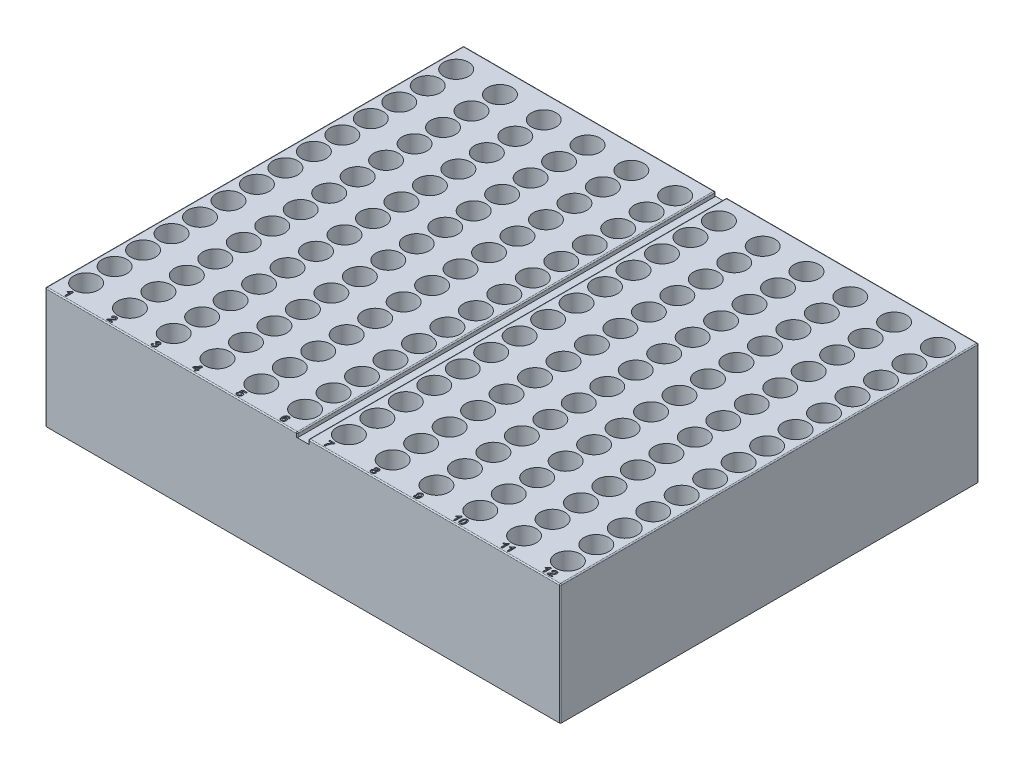
SolidWorks part; units mm, degrees
ref_plane "Front Plane" through (0, 0, 0) normal (0, 0, 1) x (1, 0, 0)
ref_plane "Top Plane" through (0, 0, 0) normal (0, 1, 0) x (1, 0, 0)
ref_plane "Right Plane" through (0, 0, 0) normal (1, 0, 0) x (0, 0, -1)
sketch "Sketch1" plane through (0, 0, 0) normal (0, 1, 0) x (1, 0, 0)
  line L0 (-50, 84.5) -> (-57.625, 84.5) construction
  line L1 (57.625, -95.5) -> (-57.625, -95.5)
  line L2 (57.625, -95.5) -> (57.625, 95.5)
  line L3 (57.625, 95.5) -> (-57.625, 95.5)
  line L4 (-57.625, -95.5) -> (-57.625, 95.5)
  line L5 (57.625, -95.5) -> (-57.625, 95.5) construction
  line L6 (57.625, 95.5) -> (-57.625, -95.5) construction
  line L7 (50, 84.5) -> (57.625, 84.5) construction
  line L8 (-50, 84.5) -> (-50, 95.5) construction
  line L9 (-30, 84.5) -> (-44.35, 84.5) construction
  line L10 (-50, -84.5) -> (-57.625, -84.5) construction
  line L11 (-50, -84.5) -> (-50, -95.5) construction
  circle A0 centre (-50, 84.5) radius 5.65
  circle A1 centre (-30, 84.5) radius 5.65
  circle A2 centre (-10, 84.5) radius 5.65
  circle A3 centre (10, 84.5) radius 5.65
  circle A4 centre (30, 84.5) radius 5.65
  circle A5 centre (50, 84.5) radius 5.65
  circle A6 centre (-50, 71.5) radius 5.65
  circle A7 centre (-30, 71.5) radius 5.65
  circle A8 centre (-10, 71.5) radius 5.65
  circle A9 centre (10, 71.5) radius 5.65
  circle A10 centre (30, 71.5) radius 5.65
  circle A11 centre (50, 71.5) radius 5.65
  circle A12 centre (-50, 58.5) radius 5.65
  circle A13 centre (-30, 58.5) radius 5.65
  circle A14 centre (-10, 58.5) radius 5.65
  circle A15 centre (10, 58.5) radius 5.65
  circle A16 centre (30, 58.5) radius 5.65
  circle A17 centre (50, 58.5) radius 5.65
  circle A18 centre (-50, 45.5) radius 5.65
  circle A19 centre (-30, 45.5) radius 5.65
  circle A20 centre (-10, 45.5) radius 5.65
  circle A21 centre (10, 45.5) radius 5.65
  circle A22 centre (30, 45.5) radius 5.65
  circle A23 centre (50, 45.5) radius 5.65
  circle A24 centre (-50, 32.5) radius 5.65
  circle A25 centre (-30, 32.5) radius 5.65
  circle A26 centre (-10, 32.5) radius 5.65
  circle A27 centre (10, 32.5) radius 5.65
  circle A28 centre (30, 32.5) radius 5.65
  circle A29 centre (50, 32.5) radius 5.65
  circle A30 centre (-50, 19.5) radius 5.65
  circle A31 centre (-30, 19.5) radius 5.65
  circle A32 centre (-10, 19.5) radius 5.65
  circle A33 centre (10, 19.5) radius 5.65
  circle A34 centre (30, 19.5) radius 5.65
  circle A35 centre (50, 19.5) radius 5.65
  circle A36 centre (-50, 6.5) radius 5.65
  circle A37 centre (-30, 6.5) radius 5.65
  circle A38 centre (-10, 6.5) radius 5.65
  circle A39 centre (10, 6.5) radius 5.65
  circle A40 centre (30, 6.5) radius 5.65
  circle A41 centre (50, 6.5) radius 5.65
  circle A42 centre (-50, -6.5) radius 5.65
  circle A43 centre (-30, -6.5) radius 5.65
  circle A44 centre (-10, -6.5) radius 5.65
  circle A45 centre (10, -6.5) radius 5.65
  circle A46 centre (30, -6.5) radius 5.65
  circle A47 centre (50, -6.5) radius 5.65
  circle A48 centre (-50, -19.5) radius 5.65
  circle A49 centre (-30, -19.5) radius 5.65
  circle A50 centre (-10, -19.5) radius 5.65
  circle A51 centre (10, -19.5) radius 5.65
  circle A52 centre (30, -19.5) radius 5.65
  circle A53 centre (50, -19.5) radius 5.65
  circle A54 centre (-50, -32.5) radius 5.65
  circle A55 centre (-30, -32.5) radius 5.65
  circle A56 centre (-10, -32.5) radius 5.65
  circle A57 centre (10, -32.5) radius 5.65
  circle A58 centre (30, -32.5) radius 5.65
  circle A59 centre (50, -32.5) radius 5.65
  circle A60 centre (-50, -45.5) radius 5.65
  circle A61 centre (-30, -45.5) radius 5.65
  circle A62 centre (-10, -45.5) radius 5.65
  circle A63 centre (10, -45.5) radius 5.65
  circle A64 centre (30, -45.5) radius 5.65
  circle A65 centre (50, -45.5) radius 5.65
  circle A66 centre (-50, -58.5) radius 5.65
  circle A67 centre (-30, -58.5) radius 5.65
  circle A68 centre (-10, -58.5) radius 5.65
  circle A69 centre (10, -58.5) radius 5.65
  circle A70 centre (30, -58.5) radius 5.65
  circle A71 centre (50, -58.5) radius 5.65
  circle A72 centre (-50, -71.5) radius 5.65
  circle A73 centre (-30, -71.5) radius 5.65
  circle A74 centre (-10, -71.5) radius 5.65
  circle A75 centre (10, -71.5) radius 5.65
  circle A76 centre (30, -71.5) radius 5.65
  circle A77 centre (50, -71.5) radius 5.65
  circle A78 centre (-50, -84.5) radius 5.65
  circle A79 centre (-30, -84.5) radius 5.65
  circle A80 centre (-10, -84.5) radius 5.65
  circle A81 centre (10, -84.5) radius 5.65
  circle A82 centre (30, -84.5) radius 5.65
  circle A83 centre (50, -84.5) radius 5.65
  point P0 (0, 0)
  dimension "D1" = 11.3
  dimension "D3" = 20
  dimension "D7" = 191
  dimension "D8" = 13
  dimension "D9" = 115.25
  dimension "D2" = 6
  dimension "D6" = 14
extrude "Boss-Extrude1" add sketch "Sketch1" along normal blind 10
sketch "Sketch2" plane through (0, 0, 0) normal (0, -1, 0) x (1, 0, 0)
  line L1 (57.625, -95.5) -> (-57.625, -95.5)
  line L2 (57.625, -95.5) -> (57.625, 95.5)
  line L3 (57.625, 95.5) -> (-57.625, 95.5)
  line L4 (-57.625, -95.5) -> (-57.625, 95.5)
  line L5 (57.625, -95.5) -> (-57.625, 95.5) construction
  line L6 (57.625, 95.5) -> (-57.625, -95.5) construction
  point P0 (0, 0)
extrude "Boss-Extrude2" add sketch "Sketch2" along normal blind 45
sketch "Sketch6" plane through (0, 0, 0) normal (0, 1, 0) x (1, 0, 0)
  circle A1 centre (-50, 84.5) radius 4.225
  circle A2 centre (-30, 84.5) radius 4.225
  circle A3 centre (-10, 84.5) radius 4.225
  circle A4 centre (10, 84.5) radius 4.225
  circle A5 centre (30, 84.5) radius 4.225
  circle A6 centre (50, 84.5) radius 4.225
  circle A7 centre (-50, 71.5) radius 4.225
  circle A8 centre (-30, 71.5) radius 4.225
  circle A9 centre (-10, 71.5) radius 4.225
  circle A10 centre (10, 71.5) radius 4.225
  circle A11 centre (30, 71.5) radius 4.225
  circle A12 centre (50, 71.5) radius 4.225
  circle A13 centre (-50, 58.5) radius 4.225
  circle A14 centre (-30, 58.5) radius 4.225
  circle A15 centre (-10, 58.5) radius 4.225
  circle A16 centre (10, 58.5) radius 4.225
  circle A17 centre (30, 58.5) radius 4.225
  circle A18 centre (50, 58.5) radius 4.225
  circle A19 centre (-50, 45.5) radius 4.225
  circle A20 centre (-30, 45.5) radius 4.225
  circle A21 centre (-10, 45.5) radius 4.225
  circle A22 centre (10, 45.5) radius 4.225
  circle A23 centre (30, 45.5) radius 4.225
  circle A24 centre (50, 45.5) radius 4.225
  circle A25 centre (-50, 32.5) radius 4.225
  circle A26 centre (-30, 32.5) radius 4.225
  circle A27 centre (-10, 32.5) radius 4.225
  circle A28 centre (10, 32.5) radius 4.225
  circle A29 centre (30, 32.5) radius 4.225
  circle A30 centre (50, 32.5) radius 4.225
  circle A31 centre (-50, 19.5) radius 4.225
  circle A32 centre (-30, 19.5) radius 4.225
  circle A33 centre (-10, 19.5) radius 4.225
  circle A34 centre (10, 19.5) radius 4.225
  circle A35 centre (30, 19.5) radius 4.225
  circle A36 centre (50, 19.5) radius 4.225
  circle A37 centre (-50, 6.5) radius 4.225
  circle A38 centre (-30, 6.5) radius 4.225
  circle A39 centre (-10, 6.5) radius 4.225
  circle A40 centre (10, 6.5) radius 4.225
  circle A41 centre (30, 6.5) radius 4.225
  circle A42 centre (50, 6.5) radius 4.225
  circle A43 centre (-50, -6.5) radius 4.225
  circle A44 centre (-30, -6.5) radius 4.225
  circle A45 centre (-10, -6.5) radius 4.225
  circle A46 centre (10, -6.5) radius 4.225
  circle A47 centre (30, -6.5) radius 4.225
  circle A48 centre (50, -6.5) radius 4.225
  circle A49 centre (-50, -19.5) radius 4.225
  circle A50 centre (-30, -19.5) radius 4.225
  circle A51 centre (-10, -19.5) radius 4.225
  circle A52 centre (10, -19.5) radius 4.225
  circle A53 centre (30, -19.5) radius 4.225
  circle A54 centre (50, -19.5) radius 4.225
  circle A55 centre (-50, -32.5) radius 4.225
  circle A56 centre (-30, -32.5) radius 4.225
  circle A57 centre (-10, -32.5) radius 4.225
  circle A58 centre (10, -32.5) radius 4.225
  circle A59 centre (30, -32.5) radius 4.225
  circle A60 centre (50, -32.5) radius 4.225
  circle A61 centre (-50, -45.5) radius 4.225
  circle A62 centre (-30, -45.5) radius 4.225
  circle A63 centre (-10, -45.5) radius 4.225
  circle A64 centre (10, -45.5) radius 4.225
  circle A65 centre (30, -45.5) radius 4.225
  circle A66 centre (50, -45.5) radius 4.225
  circle A67 centre (-50, -58.5) radius 4.225
  circle A68 centre (-30, -58.5) radius 4.225
  circle A69 centre (-10, -58.5) radius 4.225
  circle A70 centre (10, -58.5) radius 4.225
  circle A71 centre (30, -58.5) radius 4.225
  circle A72 centre (50, -58.5) radius 4.225
  circle A73 centre (-50, -71.5) radius 4.225
  circle A74 centre (-30, -71.5) radius 4.225
  circle A75 centre (-10, -71.5) radius 4.225
  circle A76 centre (10, -71.5) radius 4.225
  circle A77 centre (30, -71.5) radius 4.225
  circle A78 centre (50, -71.5) radius 4.225
  circle A79 centre (-50, -84.5) radius 4.225
  circle A80 centre (-30, -84.5) radius 4.225
  circle A81 centre (-10, -84.5) radius 4.225
  circle A82 centre (10, -84.5) radius 4.225
  circle A83 centre (30, -84.5) radius 4.225
  circle A84 centre (50, -84.5) radius 4.225
  circle A94 centre (-50, 84.5) radius 5.65 construction
  dimension "D5" = 8.45
  dimension "D3" = 13
  dimension "D4" = 20
  dimension "D1" = 6
  dimension "D2" = 14
extrude "Cut-Extrude1" cut sketch "Sketch6" against normal blind 25
shell "Shell11" [suppressed] thickness 0.5
pattern_linear "LPattern1" count 2 spacing 120 along (1, 0, 0) of bodies 106 105
sketch "Sketch7" plane through (0, 0, 95.5) normal (0, 0, 1) x (1, 0, 0)
  line L0 (-62.375, 10) -> (-57.625, 10)
  line L1 (-57.625, 10) -> (-57.625, -45)
  line L2 (-57.625, 10) -> (-57.625, -45) construction
  line L3 (-57.625, -45) -> (-62.375, -45)
  line L5 (-62.375, -45) -> (-62.375, 10)
  point P4 (0, 0)
extrude "Boss-Extrude6" add sketch "Sketch7" against normal up to vertex (191 mm away) up to point (-57.625, 10, -95.5)
sketch "Sketch8" plane through (0, 10, 0) normal (0, 1, 0) x (1, 0, 0)
  line L0 (-62.5, 95.5) -> (-62.5, -95.5)
  line L1 (-62.5, -95.5) -> (-57.5, -95.5)
  line L2 (-177.625, -95.5) -> (57.625, -95.5) construction
  line L3 (-57.5, -95.5) -> (-57.5, 95.5)
  line L4 (-57.5, 95.5) -> (-62.5, 95.5)
  line L5 (57.625, 95.5) -> (-177.625, 95.5) construction
  point P2 (-60, -95.5)
  point P3 (-57.5, 95.5)
  dimension "D1" = 5
extrude "Cut-Extrude2" cut sketch "Sketch8" against normal blind 2
sketch "Sketch5" plane through (0, 10, 0) normal (0, 1, 0) x (1, 0, 0)
  text T0 "<b>1              2              3             4              5              6              7               8              9            10             11           12  </b>" font "Arial Rounded MT Bold" height 3.5
extrude "Cut-Extrude3" cut sketch "Sketch5" against normal blind 0.5
fillet "Fillet1" radius 0.5 10 edges at (-120.0625, 10, 95.5) (0.0625, 10, 95.5) (57.625, 10, 0) (0.0625, 10, -95.5) (-177.625, 10, 0) (-120.0625, 10, -95.5) (-177.625, -17.5, -95.5) (57.625, -17.5, -95.5) (57.625, -17.5, 95.5) (-177.625, -17.5, 95.5)
fillet "Fillet2" radius 0.5 10 edges at (-57.5, 8.75, 95.5) (-57.5, 9.8536, 95.3536) (-57.5, 8.75, -95.5) (-57.5, 9.8536, -95.3536) (-62.5, 8.75, -95.5) (-62.5, 9.8536, -95.3536) (-62.5, 8.75, 95.5) (-62.5, 9.8536, 95.3536) (-57.5, 10, 0) (-62.5, 10, 0)
